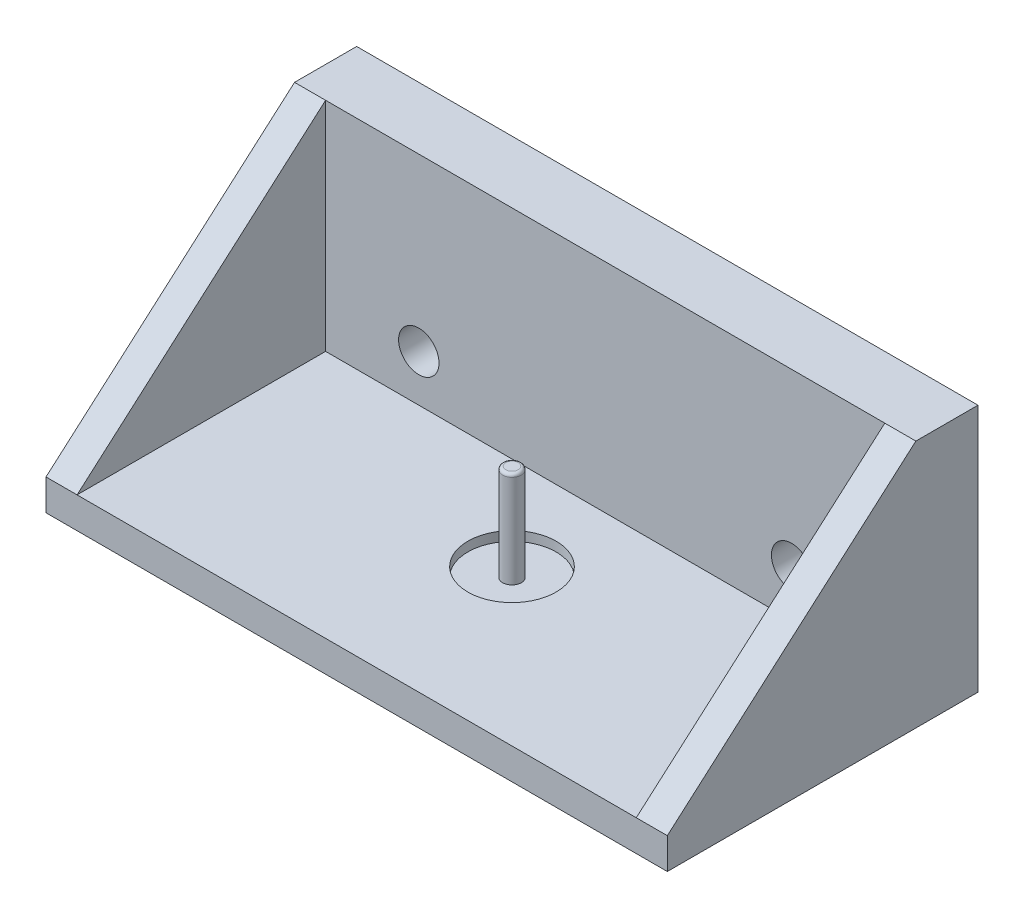
SolidWorks part; units mm, degrees
ref_plane "Front" through (0, 0, 0) normal (0, 0, 1) x (1, 0, 0)
ref_plane "Top" through (0, 0, 0) normal (0, 1, 0) x (1, 0, 0)
ref_plane "Right" through (0, 0, 0) normal (1, 0, 0) x (0, 0, -1)
sketch "Sketch1" plane through (0, 0, 0) normal (0, 1, 0) x (1, 0, 0)
  line L1 (-50, -25) -> (50, -25)
  line L2 (-50, -25) -> (-50, 25)
  line L3 (-50, 25) -> (50, 25)
  line L4 (50, -25) -> (50, 25)
  line L5 (-50, -25) -> (50, 25) construction
  line L6 (-50, 25) -> (50, -25) construction
  point P0 (0, 0)
  dimension "D1" = 100
  dimension "D2" = 50
extrude "Boss-Extrude1" add sketch "Sketch1" along normal blind 5
sketch "Sketch2" plane through (0, 0, 0) normal (0, 1, 0) x (1, 0, 0)
  line L0 (50, -25) -> (50, 25) construction
  line L1 (-50, 25) -> (50, 25)
  line L2 (-50, 25) -> (-50, 15)
  line L3 (-50, 15) -> (50, 15)
  line L4 (50, 25) -> (50, 15)
  dimension "D1" = 10
extrude "Boss-Extrude2" add sketch "Sketch2" along normal blind 40
sketch "Sketch4" plane through (0, 0, -15) normal (0, 0, 1) x (1, 0, 0)
  line L0 (0, 40) -> (-30, 40)
  line L1 (-50, 40) -> (50, 40) construction
  line L2 (-30, 40) -> (-30, 12.5)
  line L3 (0, -50) -> (0, 50) construction
  circle A0 centre (-30, 12.5) radius 3.25
  circle A1 centre (-30, 12.5) radius 6
  circle A2 centre (30, 12.5) radius 3.25
  circle A3 centre (30, 12.5) radius 6
  dimension "D3" = 6.5
  dimension "D1" = 30
  dimension "D2" = 27.5
extrude "Cut-Extrude1" cut sketch "Sketch4<3>" against normal through all both and the other way through all contours A0
sketch "Sketch4<3>" plane through (0, 0, -15) normal (0, 0, 1) x (1, 0, 0) same geometry as "Sketch4"
sketch "Sketch6" plane through (0, 0, -15) normal (0, 0, 1) x (1, 0, 0)
extrude "Cut-Extrude2" cut sketch "Sketch4" against normal through all both and the other way through all contours A2
sketch "Sketch8" plane through (50, 0, 0) normal (1, 0, 0) x (0, 0, -1)
  line L0 (15, 40) -> (15, 5)
  line L1 (15, 5) -> (-25, 5)
  line L2 (-25, 5) -> (15, 40)
extrude "Boss-Extrude5" add sketch "Sketch8" against normal blind 5 contours L2 L0 L1
mirror "Mirror1" about plane through (0, 0, 0) normal (1, 0, 0) of "Boss-Extrude5"
sketch "Sketch9" plane through (0, 5, 0) normal (0, 1, 0) x (1, 0, 0)
  circle A0 centre (0, 0) radius 7.1
  dimension "D1" = 14.2
extrude "Cut-Extrude3" cut sketch "Sketch9" against normal blind 1.5 contours A0
sketch "Sketch10" plane through (0, 3.5, 0) normal (0, 1, 0) x (1, 0, 0)
  circle A0 centre (0, 0) radius 1.5
extrude "Boss-Extrude6" add sketch "Sketch10" along normal blind 15.5
fillet "Fillet1" radius 0.5 1 edges at (0, 19, 1.5)
